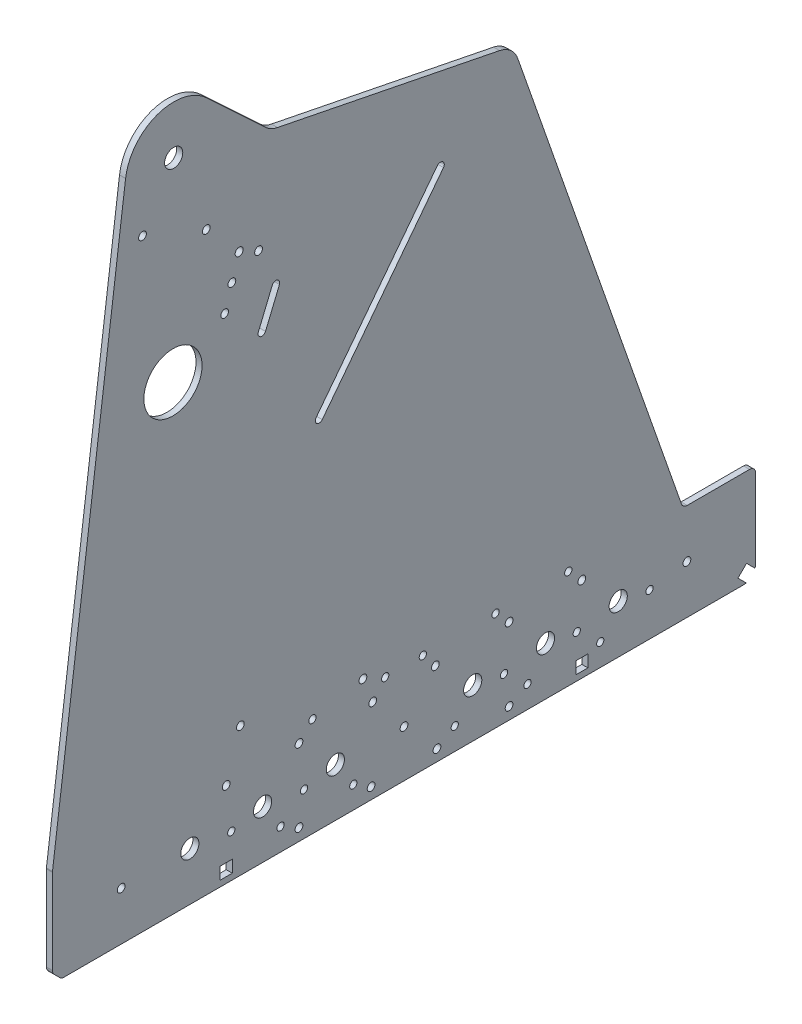
SolidWorks part; units mm, degrees
ref_plane "Front Plane" through (0, 0, 0) normal (0, 0, 1) x (1, 0, 0)
ref_plane "Top Plane" through (0, 0, 0) normal (0, 1, 0) x (1, 0, 0)
ref_plane "Right Plane" through (0, 0, 0) normal (1, 0, 0) x (0, 0, -1)
sketch "Sketch1" plane through (0, 0, 0) normal (1, 0, 0) x (0, 0, -1)
  line L0 (-184.15, -24.6062) -> (184.15, -24.6062)
  line L1 (184.15, -24.6062) -> (184.15, 26.1938)
  line L2 (184.15, 26.1938) -> (146.05, 26.1937)
  line L3 (146.05, 26.1937) -> (57.15, 280.1938)
  line L5 (-145.839, 321.5609) -> (-184.15, 26.1938)
  line L6 (-184.15, 26.1938) -> (-184.15, -24.6062)
  line L7 (-184.15, 350.0437) -> (184.15, 350.0437) construction
  line L8 (57.15, 280.1938) -> (-69.85, 305.5938)
  line L9 (-69.85, 305.5938) -> (-103.3099, 336.854)
  arc A0 (-103.3099, 336.854) -> (-145.839, 321.5609) centre (-120.65, 318.2937) ccw
  point P8 (0, -24.6062)
  dimension "D1" = 368.3
  dimension "D7" = 25.4
  dimension "D2" = 50.8
  dimension "D3" = 38.1
  dimension "D4" = 24.6062
  dimension "D5" = 374.65
  dimension "D6" = 304.8
  dimension "D8" = 342.9
  dimension "D9" = 127
  dimension "D10" = 304.8
  dimension "D11" = 25.4
  dimension "D12" = 127
extrude "Boss-Extrude1" add sketch "Sketch1" along normal blind 3.175
chamfer "Chamfer1" distance 4.7625 angle 45 2 edges at (1.5875, -24.6062, 184.15) (1.5875, -24.6062, -184.15)
fillet "Fillet1" radius 12.7 2 edges at (1.5875, 305.5938, 69.85) (1.5875, 280.1938, -57.15)
fillet "Fillet2" radius 3.175 3 edges at (1.5875, 26.1938, 184.15) (1.5875, 26.1938, -184.15) (1.5875, 26.1937, -146.05)
fillet "Fillet3" radius 3.175 4 edges at (1.5875, -19.8438, -184.15) (1.5875, -24.6062, -179.3875) (1.5875, -19.8437, 184.15) (1.5875, -24.6062, 179.3875)
sketch "Sketch16" plane through (3.175, 0, 0) normal (1, 0, 0) x (0, 0, -1)
  circle A0 centre (112.1746, 0.7937) radius 4.7625
  circle A1 centre (74.0746, 0.7937) radius 4.7625
  circle A2 centre (35.9746, 0.7937) radius 4.7625
  circle A3 centre (-35.9746, 0.7938) radius 4.7625
  circle A4 centre (-74.0746, 0.7938) radius 4.7625
  circle A5 centre (-112.1746, 0.7937) radius 4.7625
  dimension "D1" = 9.525
  dimension "D2" = 9.525
extrude "Cut-Extrude1" cut sketch "Sketch16" against normal up to next
sketch "Sketch25" plane through (3.175, 0, 0) normal (1, 0, 0) x (0, 0, -1)
  circle A0 centre (102.7672, -13.0003) radius 1.905 construction
  circle A1 centre (86.0486, 27.3622) radius 1.905 construction
  circle A2 centre (128.5804, -2.3081) radius 1.905 construction
  circle A3 centre (102.7672, -13.0003) radius 1.905
  circle A4 centre (86.0486, 27.3622) radius 1.905
  circle A5 centre (128.5804, -2.3081) radius 1.905
  circle A6 centre (64.6672, -13.0003) radius 1.905 construction
  circle A8 centre (-9.8486, 27.3622) radius 1.905 construction
  circle A10 centre (-47.9486, 27.3622) radius 1.905 construction
  circle A11 centre (-90.4804, -2.3081) radius 1.905 construction
  circle A12 centre (-64.6672, -13.0003) radius 1.905 construction
  circle A14 centre (-52.3804, -2.3081) radius 1.905 construction
  circle A15 centre (-26.5672, -13.0003) radius 1.905 construction
  circle A16 centre (9.8486, 27.3622) radius 1.905 construction
  circle A17 centre (26.5672, -13.0003) radius 1.905 construction
  circle A18 centre (47.9486, 27.3622) radius 1.905 construction
  circle A19 centre (52.3804, -2.3081) radius 1.905 construction
  circle A20 centre (90.4804, -2.3081) radius 1.905 construction
  circle A21 centre (-9.8486, 27.3622) radius 1.905
  circle A23 centre (-47.9486, 27.3622) radius 1.905
  circle A24 centre (-90.4804, -2.3081) radius 1.905
  circle A25 centre (-64.6672, -13.0003) radius 1.905
  circle A27 centre (-52.3804, -2.3081) radius 1.905
  circle A28 centre (-26.5672, -13.0003) radius 1.905
  circle A29 centre (9.8486, 27.3622) radius 1.905
  circle A30 centre (26.5672, -13.0003) radius 1.905
  circle A31 centre (47.9486, 27.3622) radius 1.905
  circle A32 centre (64.6672, -13.0003) radius 1.905
  circle A33 centre (52.3804, -2.3081) radius 1.905
  circle A34 centre (90.4804, -2.3081) radius 1.905
extrude "Cut-Extrude4" cut sketch "Sketch25" against normal up to next
sketch "Sketch23" plane through (3.175, 0, 0) normal (1, 0, 0) x (0, 0, -1)
  point P0 (-55.0246, -18.3223)
  point P3 (-55.0246, 19.9098)
  point P6 (-93.1246, 19.9098)
  point P9 (-17.2515, -18.6426)
  point P12 (-16.4124, 19.3854)
  point P15 (16.4124, 19.3854)
  point P18 (17.2515, -18.6426)
  point P21 (55.0246, -18.3223)
  point P27 (93.1246, 19.9098)
  point P30 (55.0246, 19.9098)
hole_wizard "#8 (0.16) Diameter Hole1" positions "Sketch23" profile "Sketch24" hole size "#8" standard "ANSI Inch" end condition up to next
sketch "Sketch24" plane through (3.175, -18.3223, 55.0246) normal (0, 1, 0) x (0, 0, -1)
  line L0 (0, 0) -> (0, 3.175)
  line L1 (0, 3.175) -> (2.032, 3.175)
  line L2 (2.032, 3.175) -> (2.032, 0)
  line L5 (2.032, 0) -> (0, 0)
  line L11 (0, -6.35) -> (0, 107.95) construction
  dimension "Thru Hole Dia." = 4.064
  dimension "Thru Hole Depth" = 3.175
sketch "Sketch22" plane through (3.175, 0, 0) normal (1, 0, 0) x (0, 0, -1)
  line L0 (-96.2996, -15.1473) -> (-89.9496, -15.1473) construction
  line L1 (-96.2996, -15.1473) -> (-89.9496, -15.1473)
  line L2 (-96.2996, -15.1473) -> (-96.2996, -21.4973)
  line L3 (-96.2996, -21.4973) -> (-89.9496, -21.4973)
  line L4 (-89.9496, -15.1473) -> (-89.9496, -21.4973)
  line L5 (-96.2996, -15.1473) -> (-89.9496, -21.4973) construction
  line L6 (-96.2996, -21.4973) -> (-89.9496, -15.1473) construction
  line L7 (-89.9496, -15.1473) -> (-89.9496, -19.8734) construction
  line L77 (179.3875, -24.6062) -> (183.8776, -20.1161)
  line L78 (179.3875, -24.6062) -> (174.8974, -20.1161)
  line L79 (183.8776, -20.1161) -> (179.3875, -15.626)
  line L80 (174.8974, -20.1161) -> (179.3875, -15.626)
  line L81 (180.3174, -23.6763) -> (183.2201, -20.7737) construction
  line L82 (-178.0724, -24.6062) -> (178.0724, -24.6062) construction
  line L84 (89.9496, -21.4973) -> (96.2996, -21.4973)
  line L85 (89.9496, -21.4973) -> (89.9496, -15.1473)
  line L86 (89.9496, -15.1473) -> (96.2996, -15.1473)
  line L87 (96.2996, -21.4973) -> (96.2996, -15.1473)
  line L88 (89.9496, -21.4973) -> (96.2996, -15.1473) construction
  line L89 (89.9496, -15.1473) -> (96.2996, -21.4973) construction
  point P0 (-93.1246, -18.3223)
  point P19 (93.1246, -18.3223)
  dimension "D1" = 6.35
  dimension "D2" = 6.35
extrude "Cut-Extrude3" cut sketch "Sketch22" against normal up to next
sketch "Sketch21" plane through (3.175, 0, 0) normal (1, 0, 0) x (0, 0, -1)
  circle A0 centre (-148.1579, 0.7937) radius 2.032
  circle A2 centre (0, 0) radius 2.032
  circle A3 centre (148.1579, 0.7938) radius 2.032
  dimension "D1" = 4.064
extrude "Cut-Extrude2" cut sketch "Sketch21" against normal up to next
sketch "Sketch26" plane through (3.175, 0, 0) normal (1, 0, 0) x (0, 0, -1)
  line L0 (-145.839, 321.5609) -> (-184.1236, 26.3971) construction
  line L1 (-178.0724, -24.6062) -> (178.0724, -24.6062) construction
  circle A0 centre (-121.0218, 216.6937) radius 15.24
  dimension "D1" = 30.48
  dimension "D2" = 38.1
  dimension "D3" = 241.3
extrude "Cut-Extrude5" cut sketch "Sketch26" against normal through all
sketch "Sketch27" plane through (3.175, 0, 0) normal (1, 0, 0) x (0, 0, -1)
  circle A0 centre (-120.65, 318.2937) radius 4.7625
  dimension "D1" = 9.525
extrude "Cut-Extrude6" cut sketch "Sketch27" against normal through all
sketch "Sketch28" plane through (3.175, 0, 0) normal (1, 0, 0) x (0, 0, -1)
  line L0 (-120.65, 318.2937) -> (-103.5612, 277.2599) construction
  line L1 (-103.5612, 277.2599) -> (-86.3654, 258.566) construction
  line L2 (-86.3654, 258.566) -> (-90.1612, 246.4465) construction
  line L3 (-90.1612, 246.4465) -> (-93.9569, 234.327) construction
  line L4 (-145.839, 321.5609) -> (-184.1236, 26.3971) construction
  circle A0 centre (-93.9569, 234.327) radius 2.032
  circle A1 centre (-90.1612, 246.4465) radius 2.032
  circle A2 centre (-86.3654, 258.566) radius 2.0955
  circle A3 centre (-103.5612, 277.2599) radius 2.032
  dimension "D4" = 4.064
  dimension "D5" = 4.191
  dimension "D6" = 4.064
  dimension "D1" = 25.4
  dimension "D2" = 44.45
  dimension "D3" = 12.7
  dimension "D7" = 30
  dimension "D8" = 120
  dimension "D9" = 160
extrude "Cut-Extrude7" cut sketch "Sketch28" against normal through all
sketch "Sketch29" plane through (3.175, 0, 0) normal (1, 0, 0) x (0, 0, -1)
  line L0 (-145.839, 321.5609) -> (-184.1236, 26.3971) construction
  line L1 (-67.1375, 233.9197) -> (-74.4276, 216.3198) construction
  line L2 (-65.2602, 233.1421) -> (-72.5503, 215.5422)
  line L3 (-69.0148, 234.6973) -> (-76.305, 217.0974)
  line L4 (-67.1375, 233.9197) -> (-67.1375, 253.7354) construction
  circle A0 centre (-136.9875, 291.0697) radius 2.032
  circle A2 centre (-120.65, 318.2937) radius 4.7625 construction
  arc A4 (-65.2602, 233.1421) -> (-69.0148, 234.6973) centre (-67.1375, 233.9197) ccw
  arc A5 (-76.305, 217.0974) -> (-72.5503, 215.5422) centre (-74.4276, 216.3198) ccw
  point P8 (-70.7826, 225.1198)
  dimension "D1" = 31.75
  dimension "D2" = 4.064
  dimension "D3" = 69.85
  dimension "D4" = 12.7
  dimension "D5" = 57.15
  dimension "D6" = 19.05
  dimension "D7" = 22.5
extrude "Cut-Extrude8" cut sketch "Sketch29" against normal through all
sketch "Sketch30" plane through (3.175, 0, 0) normal (1, 0, 0) x (0, 0, -1)
  line L0 (-85.7125, 43.2475) -> (-21.5354, 32.3996) construction
  circle A1 centre (-21.5354, 32.3996) radius 7.9375 construction
  circle A2 centre (-85.7125, 43.2475) radius 2.032
  circle A3 centre (-35.9746, 0.7938) radius 4.7625 construction
  circle A4 centre (-48.1454, 36.8975) radius 19.05 construction
  circle A5 centre (-85.7125, 43.2475) radius 19.05 construction
  circle A6 centre (-21.5354, 32.3996) radius 2.032
  circle A7 centre (-74.0746, 0.7938) radius 4.7625 construction
  point P4 (-48.1454, 36.8975)
  dimension "D2" = 38.1
  dimension "D4" = 15.875
  dimension "D5" = 4.064
  dimension "D6" = 44.45
  dimension "D1" = 38.1
  dimension "D3" = 6.35
extrude "Cut-Extrude9" cut sketch "Sketch30" against normal through all
sketch "Sketch31" plane through (0, 0, 0) normal (-1, 0, 0) x (0, 0, 1)
  circle A0 centre (-19.05, 244.475) radius 2.032
  circle A1 centre (76.2, 254) radius 2.032
  dimension "D1" = 19.05
  dimension "D3" = 4.064
  dimension "D4" = 76.2
  dimension "D6" = 4.064
  dimension "D2" = 244.475
  dimension "D5" = 254
extrude "Cut-Extrude10" cut sketch "Sketch31" against normal through all
sketch "Sketch34" plane through (0, 0, 0) normal (-1, 0, 0) x (0, 0, 1)
  line L0 (44.45, 161.925) -> (-19.05, 244.475) construction
  line L1 (42.8394, 160.6861) -> (-20.6606, 243.2361)
  line L2 (46.0606, 163.1639) -> (-17.4394, 245.7139)
  arc A0 (42.8394, 160.6861) -> (46.0606, 163.1639) centre (44.45, 161.925) ccw
  arc A1 (-17.4394, 245.7139) -> (-20.6606, 243.2361) centre (-19.05, 244.475) ccw
  point P3 (12.7, 203.2)
  dimension "D5" = 2.032
  dimension "D1" = 161.925
  dimension "D2" = 44.45
  dimension "D3" = 244.475
  dimension "D4" = 19.05
extrude "Cut-Extrude12" cut sketch "Sketch34" against normal through all
sketch "Sketch35" plane through (0, 0, 0) normal (-1, 0, 0) x (0, 0, 1)
  circle A0 centre (146.05, 247.65) radius 2.032
  dimension "D1" = 4.064
  dimension "D2" = 247.65
  dimension "D3" = 146.05
extrude "Cut-Extrude13" [suppressed] cut sketch "Sketch35" against normal through all
